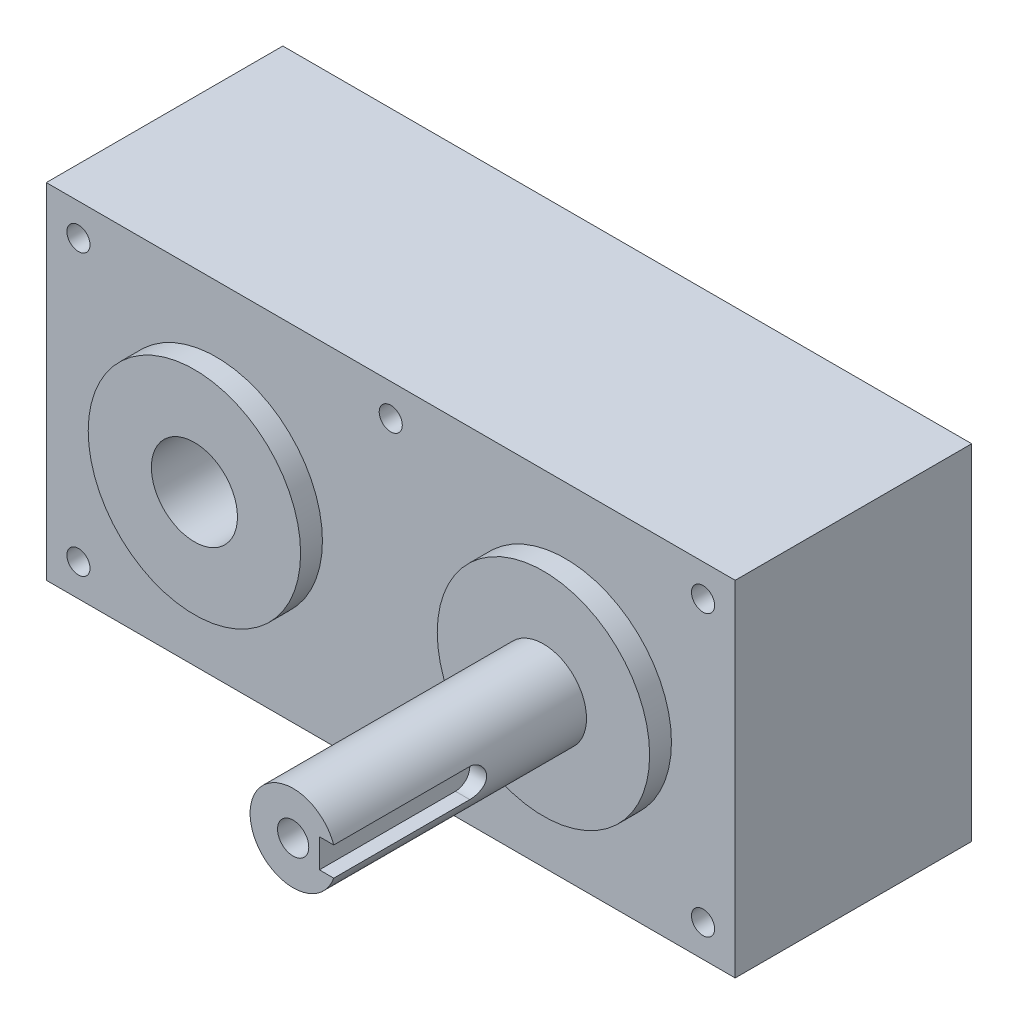
SolidWorks part; units mm, degrees
ref_plane "Front Plane" through (0, 0, 0) normal (0, 0, 1) x (1, 0, 0)
ref_plane "Top Plane" through (0, 0, 0) normal (0, 1, 0) x (1, 0, 0)
ref_plane "Right Plane" through (0, 0, 0) normal (1, 0, 0) x (0, 0, -1)
sketch "Sketch1" plane through (0, 0, 0) normal (0, 0, 1) x (1, 0, 0)
  line L1 (0, 0) -> (152.4, 0)
  line L2 (0, 0) -> (0, 76.2)
  line L3 (0, 76.2) -> (152.4, 76.2)
  line L4 (152.4, 0) -> (152.4, 76.2)
  dimension "D1" = 152.4
  dimension "D2" = 76.2
extrude "Boss-Extrude1" add sketch "Sketch1" along normal blind 52.324
ref_plane "Plane1" through (0, 38.1, 0) normal (0, 1, 0) x (-1, 0, 0)
hole_wizard "1/4-20 Tapped Hole1" positions "Sketch3" profile "Sketch2" tap size "1/4-20" standard "Ansi Inch"
sketch "Sketch3" plane through (0, 0, 52.324) normal (0, 0, 1) x (1, 0, 0)
  line L0 (76.2, 76.2) -> (76.2, 69.088) construction
  line L1 (152.4, 76.2) -> (0, 76.2) construction
  line L3 (28.7782, 38.1) -> (-28.7782, 38.1) construction
  point P0 (76.2, 69.088)
  point P1 (7.112, 69.088)
  point P3 (145.288, 69.088)
  dimension "D1" = 30.988
  dimension "D2" = 69.088
  dimension "D3" = 69.088
sketch "Sketch2" plane through (76.2, 69.088, 52.324) normal (1, 0, 0) x (0, -1, 0)
  line L0 (0, 0) -> (0, 18.0438)
  line L1 (0, 18.0438) -> (2.5527, 16.51)
  line L2 (2.5527, 16.51) -> (2.5527, 0)
  line L5 (2.5527, 0) -> (0, 0)
  line L10 (0, 18.0438) -> (-2.5527, 16.51) construction
  line L11 (0, -6.35) -> (0, 107.95) construction
  dimension "Tap Drill Dia." = 5.1054
  dimension "Tap Drill Depth" = 16.51
  dimension "Drill Angle" = 118
mirror "Mirror1" about plane through (0, 38.1, 0) normal (0, 1, 0) of "1/4-20 Tapped Hole1"
sketch "Sketch4" plane through (0, 0, 52.324) normal (0, 0, 1) x (1, 0, 0)
  line L0 (28.7782, 38.1) -> (-28.7782, 38.1) construction
  line L1 (76.2, 76.2) -> (76.2, 0) construction
  line L2 (152.4, 76.2) -> (0, 76.2) construction
  line L3 (0, 0) -> (152.4, 0) construction
  circle A0 centre (37.592, 38.1) radius 23.495
  circle A1 centre (114.808, 38.1) radius 23.495
  dimension "D1" = 46.99
  dimension "D2" = 38.608
  dimension "D3" = 38.608
extrude "Boss-Extrude2" add sketch "Sketch4" along normal blind 4.826
sketch "Sketch5" plane through (0, 0, 52.324) normal (0, 0, 1) x (1, 0, 0)
  circle A0 centre (114.808, 38.1) radius 9.525
  dimension "D1" = 19.05
extrude "Boss-Extrude3" add sketch "Sketch5" along normal blind 60.198
sketch "Sketch6" plane through (0, 0, 112.522) normal (0, 0, 1) x (1, 0, 0)
  line L0 (114.808, 38.1) -> (124.333, 38.1) construction
  line L1 (120.6133, 34.925) -> (120.6133, 41.275)
  line L2 (120.6133, 41.275) -> (123.7883, 41.275)
  line L3 (120.6133, 34.925) -> (123.7883, 34.925)
  circle A1 centre (114.808, 38.1) radius 9.525
  arc A2 (123.7883, 34.925) -> (123.7883, 41.275) centre (114.808, 38.1) ccw
  point P9 (120.6133, 38.1)
  dimension "D2" = 6.35
  dimension "D3" = 3.175
  dimension "D1" = 0
extrude "Cut-Extrude1" cut sketch "Sketch6" against normal blind 33.274
fillet "Fillet1" 2 edges at (122.2008, 41.275, 79.248) (122.2008, 34.925, 79.248) type full round first side face at (122.2008, 41.275, 95.885) second side face at (122.2008, 34.925, 95.885) middle face at (122.3369, 38.1, 79.248)
sketch "Sketch7" plane through (0, 0, 57.15) normal (0, 0, 1) x (1, 0, 0)
  circle A0 centre (37.592, 38.1) radius 9.525
  dimension "D1" = 19.05
extrude "Cut-Extrude2" cut sketch "Sketch7" against normal through all
hole_wizard "5/16-24 Tapped Hole1" positions "Sketch9" profile "Sketch8" tap size "5/16-24" standard "Ansi Inch"
sketch "Sketch9" plane through (0, 0, 112.522) normal (0, 0, 1) x (1, 0, 0)
  arc A0 (123.7883, 41.275) -> (123.7883, 34.925) centre (114.808, 38.1) ccw construction
  point P0 (114.808, 38.1)
sketch "Sketch8" plane through (114.808, 38.1, 112.522) normal (1, 0, 0) x (0, -1, 0)
  line L0 (0, 0) -> (0, 21.1356)
  line L1 (0, 21.1356) -> (3.4544, 19.06)
  line L2 (3.4544, 19.06) -> (3.4544, 0)
  line L5 (3.4544, 0) -> (0, 0)
  line L10 (0, 21.1356) -> (-3.4544, 19.06) construction
  line L11 (0, -6.35) -> (0, 107.95) construction
  dimension "Tap Drill Dia." = 6.9088
  dimension "Tap Drill Depth" = 19.06
  dimension "Drill Angle" = 118
equation "\"D3@Sketch3\" = \"D2@Sketch3\""
equation "\"D3@Sketch4\" = \"D2@Sketch4\""
